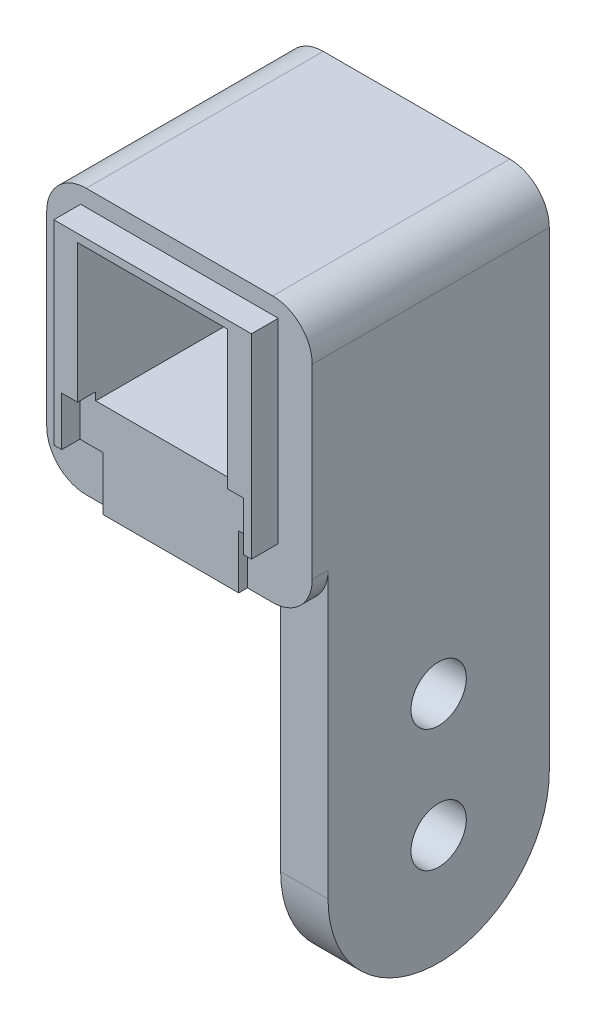
SolidWorks part; units mm, degrees
ref_plane "Front Plane" through (0, 0, 0) normal (0, 0, 1) x (1, 0, 0)
ref_plane "Top Plane" through (0, 0, 0) normal (0, 1, 0) x (1, 0, 0)
ref_plane "Right Plane" through (0, 0, 0) normal (1, 0, 0) x (0, 0, -1)
sketch "Sketch1" plane through (0, 0, 0) normal (0, 0, 1) x (1, 0, 0)
  line L1 (-16.3079, 17.6796) -> (17.2921, 17.6796)
  line L2 (-16.3079, 17.6796) -> (-16.3079, -15.9204)
  line L3 (-16.3079, -15.9204) -> (17.2921, -15.9204)
  line L4 (17.2921, 17.6796) -> (17.2921, -15.9204)
  line L5 (-9.0079, 14.5796) -> (9.9921, 14.5796)
  line L6 (-9.0079, 14.5796) -> (-9.0079, -3.9204)
  line L7 (-9.0079, -3.9204) -> (9.9921, -3.9204)
  line L8 (9.9921, 14.5796) -> (9.9921, -3.9204)
  line L9 (-12.0079, 15.5796) -> (12.9921, 15.5796)
  line L10 (-12.0079, 15.5796) -> (-12.0079, -9.1204)
  line L11 (-12.0079, -9.1204) -> (12.9921, -9.1204)
  line L12 (12.9921, 15.5796) -> (12.9921, -9.1204)
  dimension "D1" = 33.6
  dimension "D2" = 33.6
  dimension "D3" = 3.1
  dimension "D4" = 12
  dimension "D5" = 7.3
  dimension "D6" = 7.3
  dimension "D7" = 4.3
  dimension "D8" = 4.3
  dimension "D9" = 2.1
  dimension "D10" = 6.8
extrude "Boss-Extrude1" add sketch "Sketch1" along normal blind 3.4 contours L12 L9 L10 L11 L5 L8 L7 L6 region at (0.4921, 15.2281, 0)
extrude "Boss-Extrude2" add sketch "Sketch1<3>" against normal blind 27 contours L12 L9 L10 L11 L5 L8 L7 L6 | L4 L1 L2 L3 L9 L12 L11 L10 region at (0.4921, 17.2044, 0) region at (0.4921, 15.2281, 0)
sketch "Sketch1<3>" plane through (0, 0, 0) normal (0, 0, 1) x (1, 0, 0) same geometry as "Sketch1"
sketch "Sketch2" plane through (0, 0, -27) normal (0, 0, -1) x (-1, 0, 0)
  line L1 (-17.2921, 17.6796) -> (16.3079, 17.6796)
  line L2 (-17.2921, 17.6796) -> (-17.2921, -15.9204)
  line L3 (-17.2921, -15.9204) -> (16.3079, -15.9204)
  line L4 (16.3079, 17.6796) -> (16.3079, -15.9204)
extrude "Boss-Extrude3" add sketch "Sketch2" along normal blind 3
sketch "Sketch3" plane through (17.2921, 0, 0) normal (1, 0, 0) x (0, 0, -1)
  line L0 (16, -46.9204) -> (30, -46.9204)
  line L1 (30, -46.9204) -> (2, -46.9204)
  line L2 (30, -46.9204) -> (30, -15.9204)
  line L3 (30, -15.9204) -> (0, -15.9204) construction
  line L4 (2, -46.9204) -> (2, -15.9204)
  line L5 (2, -15.9204) -> (30, -15.9204)
  line L6 (30, 17.6796) -> (30, -15.9204) construction
  line L7 (16, -46.9204) -> (16, -15.9204)
  line L8 (16, -15.9204) -> (16, -31.4204)
  circle A0 centre (16, -46.9204) radius 14
  circle A1 centre (16, -46.9204) radius 3.5
  circle A2 centre (16, -31.4204) radius 3.5
  line M3 (0, -15.9204) -> (30, -15.9204)
  dimension "D1" = 28
  dimension "D2" = 7
  dimension "D5" = 7
  dimension "D3" = 31
  dimension "D4" = 0
  dimension "D6" = 15.5
extrude "Boss-Extrude4" add sketch "Sketch3" against normal blind 6 contours A2 L8 L4 A0 M3 | A2 A0 L2 L5 L8 | A2 L7 A1 L1 A0 | A2 A0 L1 A1 L7 | A1 L1 A0 region at (17.2921, -40.8871, -22.3906) region at (17.2921, -53.1593, -16) region at (17.2921, -40.8871, -9.6094) region at (17.2921, -25.9059, -23.9228) region at (17.2921, -25.9059, -8.0772)
fillet "Fillet1" radius 5 4 edges at (17.2921, -15.9204, -1) (-16.3079, -15.9204, -15) (17.2921, 17.6796, -15) (-16.3079, 17.6796, -15)
sketch "Sketch4" plane through (0, 0, 3.4) normal (0, 0, 1) x (1, 0, 0)
  line L0 (-9.0079, -3.9204) -> (9.9921, -3.9204) construction
  line L1 (-8.5079, -3.9204) -> (9.4921, -3.9204)
  line L2 (-8.5079, -3.9204) -> (-8.5079, -9.1204)
  line L3 (-8.5079, -9.1204) -> (9.4921, -9.1204)
  line L4 (9.4921, -3.9204) -> (9.4921, -9.1204)
  line L5 (-12.0079, -9.1204) -> (12.9921, -9.1204) construction
  line L7 (9.4921, -3.9204) -> (9.9921, -3.9204)
  line L8 (-8.5079, -3.9204) -> (-9.0079, -3.9204)
  line M7 (-12.0079, -9.1204) -> (12.9921, -9.1204)
  line M10 (9.9921, -3.9204) -> (-9.0079, -3.9204)
  dimension "D1" = 18
  dimension "D2" = 0.5
  dimension "D3" = 0.5
extrude "Cut-Extrude1" cut sketch "Sketch4" against normal blind 2.3 contours L4 L2 M10 M7 region at (0.4921, -6.5204, 3.4)
sketch "Sketch5" plane through (0, 0, 0) normal (0, 0, 1) x (1, 0, 0)
  line L0 (-8.5079, -9.1204) -> (-8.1079, -9.1204)
  line L1 (-8.5079, -9.1204) -> (9.4921, -9.1204) construction
  line L2 (9.4921, -9.1204) -> (9.0921, -9.1204)
  line L3 (-11.3079, -15.9204) -> (12.2921, -15.9204) construction
  line L4 (-8.1079, -9.1204) -> (9.0921, -9.1204)
  line L5 (-8.1079, -9.1204) -> (-8.1079, -15.9204)
  line L6 (-8.1079, -15.9204) -> (9.0921, -15.9204)
  line L7 (9.0921, -9.1204) -> (9.0921, -15.9204)
  line M3 (12.9921, -9.1204) -> (-12.0079, -9.1204)
  line M5 (-11.3079, -15.9204) -> (12.2921, -15.9204)
extrude "Boss-Extrude5" add sketch "Sketch5" along normal blind 1.1 contours L7 L5 M3 M5 region at (0.4921, -12.5204, 0)
sketch "Sketch6" plane through (0, 0, 3.4) normal (0, 0, 1) x (1, 0, 0)
  line L0 (12.9921, 15.5796) -> (12.9921, -9.1204) construction
  line L1 (-12.0079, -9.1204) -> (12.9921, -9.1204)
  line L2 (-12.0079, -9.1204) -> (-12.0079, -2.9204)
  line L3 (-12.0079, -2.9204) -> (12.9921, -2.9204)
  line L4 (12.9921, -9.1204) -> (12.9921, -2.9204)
extrude "Cut-Extrude2" cut sketch "Sketch6" against normal blind 2.3
sketch "Sketch7" plane through (0, -2.9204, 0) normal (0, -1, 0) x (1, 0, 0)
  line L0 (-9.0079, 1.1) -> (-12.0079, 1.1) construction
  line L1 (-12.0079, 3.4) -> (-11.0079, 3.4)
  line L2 (-12.0079, 3.4) -> (-12.0079, 1.1)
  line L3 (-12.0079, 1.1) -> (-11.0079, 1.1)
  line L4 (-11.0079, 3.4) -> (-11.0079, 1.1)
  line L5 (12.9921, 1.1) -> (9.9921, 1.1) construction
  line L6 (12.9921, 3.4) -> (11.9921, 3.4)
  line L7 (12.9921, 3.4) -> (12.9921, 1.1)
  line L8 (12.9921, 1.1) -> (11.9921, 1.1)
  line L9 (11.9921, 3.4) -> (11.9921, 1.1)
  dimension "D1" = 1
  dimension "D2" = 1
extrude "Boss-Extrude6" add sketch "Sketch7" along normal blind 6.2
equation "\"D2@Sketch1\"=\"D1@Sketch1\""
equation "\"D4@Sketch1\"=5.2+\"D10@Sketch1\""
equation "\"D6@Sketch1\"=\"D5@Sketch1\""
equation "\"D8@Sketch1\"=\"D7@Sketch1\""
equation "\"D1@Boss-Extrude1\"=8.2-4.8"
equation "\"D5@Sketch3\"=\"D2@Sketch3\""
